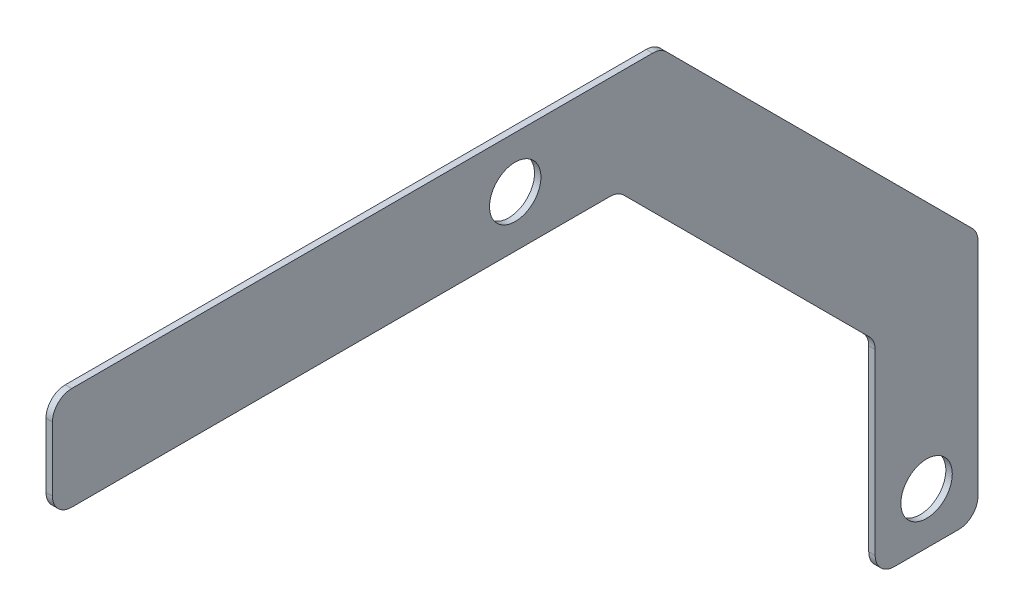
SolidWorks part; units mm, degrees
material "6063-O"
ref_plane "Front" through (0, 0, 0) normal (0, 0, 1) x (1, 0, 0)
ref_plane "Top" through (0, 0, 0) normal (0, 1, 0) x (1, 0, 0)
ref_plane "Right" through (0, 0, 0) normal (1, 0, 0) x (0, 0, -1)
sketch "Sketch1" plane through (0, 0, 0) normal (1, 0, 0) x (0, 0, -1)
  line L0 (0, 25.4) -> (0, -25.4) construction
  line L1 (-228.6, 25.4) -> (228.6, 25.4)
  line L2 (-228.6, 25.4) -> (-228.6, -254)
  line L3 (-177.8, -25.4) -> (177.8, -25.4)
  line L4 (228.6, 25.4) -> (228.6, -254)
  line L7 (228.6, -254) -> (177.8, -254)
  line L8 (177.8, -25.4) -> (177.8, -254)
  line L11 (-228.6, -254) -> (-177.8, -254)
  line L12 (-177.8, -25.4) -> (-177.8, -254)
  circle A0 centre (0, 0) radius 12.7
  point P12 (0, 0)
  dimension "D5" = 25.4
  dimension "D1" = 50.8
  dimension "D2" = 50.8
  dimension "D3" = 457.2
  dimension "D4" = 228.6
extrude "Boss-Extrude1" add sketch "Sketch1" along normal blind 3.175
sketch "Sketch3" plane through (3.175, 0, 0) normal (1, 0, 0) x (0, 0, -1)
  line L0 (-279.2989, -228.6) -> (49720.7011, -228.6) construction
  line L1 (-228.6, -254) -> (-177.8, -254) construction
  line L2 (-203.2, -254) -> (-203.2, 25.4) construction
  line L3 (228.6, 25.4) -> (-228.6, 25.4) construction
  line L4 (203.2, -254) -> (203.2, 25.4) construction
  line L5 (177.8, -254) -> (228.6, -254) construction
  circle A0 centre (-203.2, -228.6) radius 12.7
  circle A1 centre (203.2, -228.6) radius 12.7
  point P12 (-203.2, -228.6)
  point P13 (203.2, -228.6)
  dimension "D2" = 25.4
  dimension "D1" = 25.4
extrude "Cut-Extrude1" cut sketch "Sketch3" against normal through all
sketch "Sketch4" plane through (3.175, 0, 0) normal (1, 0, 0) x (0, 0, -1)
  line L1 (-177.8, -25.4) -> (-228.6, -25.4)
  line L2 (-177.8, -25.4) -> (-177.8, -254)
  line L3 (-177.8, -254) -> (-228.6, -254)
  line L4 (-228.6, -25.4) -> (-228.6, -254)
extrude "Cut-Extrude2" cut sketch "Sketch4" against normal through all
sketch "Sketch5" plane through (3.175, 0, 0) normal (1, 0, 0) x (0, 0, -1)
  line L0 (50.8, -25.4) -> (177.8, -152.4)
  line L1 (-228.6, -25.4) -> (177.8, -25.4) construction
  line L2 (177.8, -25.4) -> (177.8, -254) construction
  line L3 (50.8, -25.4) -> (177.8, -25.4)
  line L4 (177.8, -25.4) -> (177.8, -152.4)
  dimension "D1" = 45
  dimension "D2" = 127
extrude "Boss-Extrude2" add sketch "Sketch5" against normal blind 3.175
sketch "Sketch6" plane through (3.175, 0, 0) normal (1, 0, 0) x (0, 0, -1)
  line L0 (71.842, 25.4) -> (228.6, -131.358)
  line L1 (228.6, 25.4) -> (-228.6, 25.4) construction
  line L2 (228.6, -254) -> (228.6, 25.4) construction
  line L3 (228.6, -131.358) -> (228.6, 25.4)
  line L4 (228.6, 25.4) -> (71.842, 25.4)
  line L9 (50.8, -25.4) -> (177.8, -152.4) construction
  point P6 (228.6, -144.8547)
  dimension "D1" = 50.8
extrude "Cut-Extrude3" cut sketch "Sketch6" against normal through all
fillet "Fillet1" radius 9.525 8 edges at (1.5875, -254, -228.6) (1.5875, -254, -177.8) (1.5875, -152.4, -177.8) (1.5875, -131.358, -228.6) (1.5875, 25.4, -71.842) (1.5875, -25.4, -50.8) (1.5875, -25.4, 228.6) (1.5875, 25.4, 228.6)
